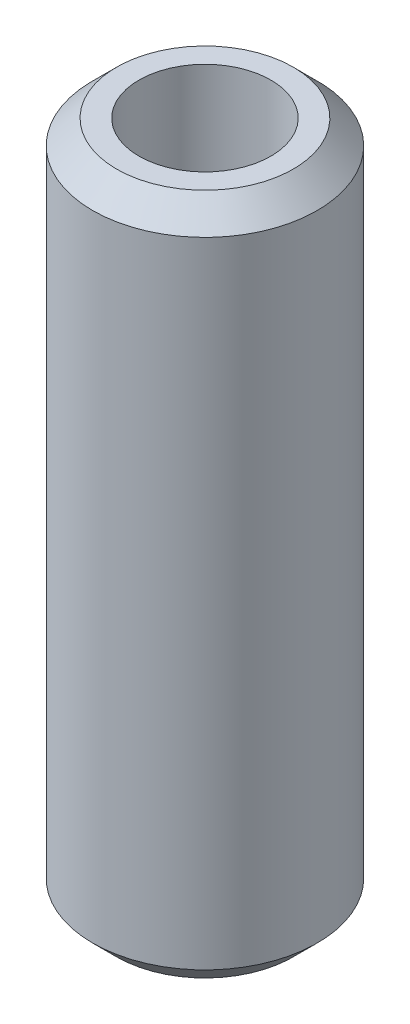
SolidWorks part; units mm, degrees
ref_plane "Front Plane" through (0, 0, 0) normal (0, 0, 1) x (1, 0, 0)
ref_plane "Top Plane" through (0, 0, 0) normal (0, 1, 0) x (1, 0, 0)
ref_plane "Right Plane" through (0, 0, 0) normal (1, 0, 0) x (0, 0, -1)
sketch "Sketch1" plane through (0, 0, 0) normal (0, 1, 0) x (1, 0, 0)
  circle A0 centre (0, 0) radius 7.5
  dimension "SHAFT_OD" = 15
extrude "Boss-Extrude1" add sketch "Sketch1" along normal blind 45.5729
sketch "Sketch2" plane through (0, 0, 0) normal (0, 1, 0) x (1, 0, 0)
  circle A0 centre (0, 0) radius 4.4061
  dimension "BORE_D" = 8.8123
extrude "Cut-Extrude1" cut sketch "Sketch2" along normal through all
chamfer "Chamfer1" distance 1.5976 angle 45 2 edges at (0, 45.5729, 7.5) (0, 0, 7.5)
